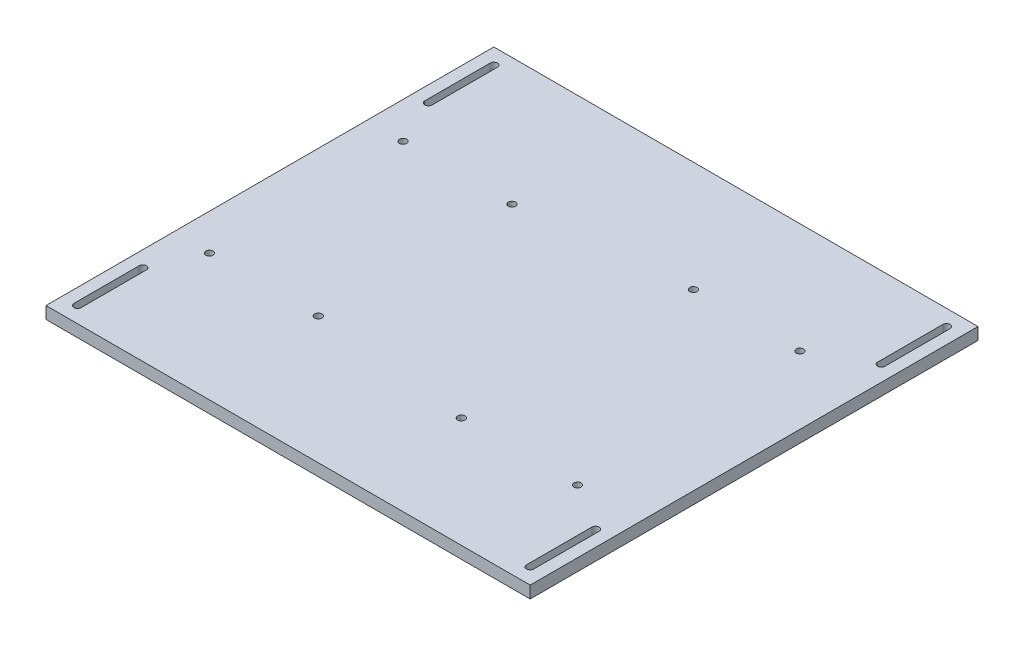
SolidWorks part; units mm, degrees
ref_plane "Front Plane" through (0, 0, 0) normal (0, 0, 1) x (1, 0, 0)
ref_plane "Top Plane" through (0, 0, 0) normal (0, 1, 0) x (1, 0, 0)
ref_plane "Right Plane" through (0, 0, 0) normal (1, 0, 0) x (0, 0, -1)
sketch "Sketch2" plane through (0, 0, 0) normal (0, 1, 0) x (1, 0, 0)
  line L0 (-93.5, 59) -> (-93.5, 86) construction
  line L1 (-100, -92.5) -> (100, -92.5)
  line L2 (-100, -92.5) -> (-100, 92.5)
  line L3 (-100, 92.5) -> (100, 92.5)
  line L4 (100, -92.5) -> (100, 92.5)
  line L5 (-100, -92.5) -> (100, 92.5) construction
  line L6 (-100, 92.5) -> (100, -92.5) construction
  line L7 (-95, 59) -> (-95, 86)
  line L8 (-92, 59) -> (-92, 86)
  line L9 (-100, 0) -> (100, 0) construction
  line L10 (100, 0) -> (0, 92.5) construction
  line L11 (0, 92.5) -> (0, -92.5) construction
  line L12 (93.5, 59) -> (93.5, 86) construction
  line L13 (95, 59) -> (95, 86)
  line L14 (92, 59) -> (92, 86)
  line L15 (93.5, -59) -> (93.5, -86) construction
  line L16 (95, -59) -> (95, -86)
  line L17 (92, -59) -> (92, -86)
  line L18 (-93.5, -59) -> (-93.5, -86) construction
  line L19 (-95, -59) -> (-95, -86)
  line L20 (-92, -59) -> (-92, -86)
  arc A0 (-95, 59) -> (-92, 59) centre (-93.5, 59) ccw
  arc A1 (-92, 86) -> (-95, 86) centre (-93.5, 86) ccw
  arc A2 (95, 59) -> (92, 59) centre (93.5, 59) cw
  arc A3 (92, 86) -> (95, 86) centre (93.5, 86) cw
  arc A4 (95, -59) -> (92, -59) centre (93.5, -59) ccw
  arc A5 (92, -86) -> (95, -86) centre (93.5, -86) ccw
  arc A6 (-95, -59) -> (-92, -59) centre (-93.5, -59) cw
  arc A7 (-92, -86) -> (-95, -86) centre (-93.5, -86) cw
  point P0 (0, 0)
  point P8 (-93.5, 72.5)
  point P19 (93.5, 72.5)
  point P26 (93.5, -72.5)
  point P33 (-93.5, -72.5)
  dimension "D4" = 1.5
  dimension "D1" = 200
  dimension "D2" = 185
  dimension "D3" = 27
  dimension "D5" = 5
  dimension "D6" = 6.5
extrude "Boss-Extrude1" add sketch "Sketch2" along normal blind 5
sketch "Sketch3" plane through (0, 5, 0) normal (0, 1, 0) x (1, 0, 0)
  line L0 (-100, 0) -> (100, 0) construction
  line L1 (-100, 92.5) -> (-100, -92.5) construction
  line L2 (100, -92.5) -> (100, 92.5) construction
  line L3 (100, 0) -> (0, -92.5) construction
  line L4 (-100, -92.5) -> (100, -92.5) construction
  line L5 (0, -92.5) -> (0, 92.5) construction
  line L6 (100, 92.5) -> (-100, 92.5) construction
  line L7 (-62.5, -50) -> (-62.5, 55.3864) construction
  line L8 (-30, -50) -> (-95, -50)
  line L9 (-30, -50) -> (-30, 50)
  line L10 (-30, 50) -> (-95, 50)
  line L11 (-95, -50) -> (-95, 50)
  line L12 (-30, -50) -> (-95, 50) construction
  line L13 (-30, 50) -> (-95, -50) construction
  circle A0 centre (-85, -40) radius 1.5
  circle A1 centre (-85, 40) radius 1.5
  circle A2 centre (-40, 40) radius 1.5
  circle A3 centre (-40, -40) radius 1.5
  point P9 (-62.5, 0)
  dimension "D4" = 3
  dimension "D1" = 65
  dimension "D2" = 100
  dimension "D3" = 5
  dimension "D5" = 10
  dimension "D6" = 10
extrude "Cut-Extrude1" cut sketch "Sketch3" against normal through all contours A0 | A1 | A3 | A2
sketch "Sketch4" plane through (0, 5, 0) normal (0, 1, 0) x (1, 0, 0)
  line L0 (-100, 0) -> (100, 0) construction
  line L1 (-100, 92.5) -> (-100, -92.5) construction
  line L2 (100, -92.5) -> (100, 92.5) construction
  line L3 (50, 92.5) -> (50, -92.5) construction
  line L4 (100, 92.5) -> (-100, 92.5) construction
  line L5 (-100, -92.5) -> (100, -92.5) construction
  circle A0 centre (28, 46.935) radius 1.5
  circle A1 centre (72, 46.935) radius 1.5
  circle A2 centre (26, -46.935) radius 1.5
  circle A3 centre (74, -46.935) radius 1.5
  dimension "D1" = 3
  dimension "D4" = 3
  dimension "D7" = 46.935
  dimension "D2" = 50
  dimension "D3" = 44
  dimension "D5" = 48
  dimension "D6" = 93.87
extrude "Cut-Extrude3" cut sketch "Sketch4" against normal through all
